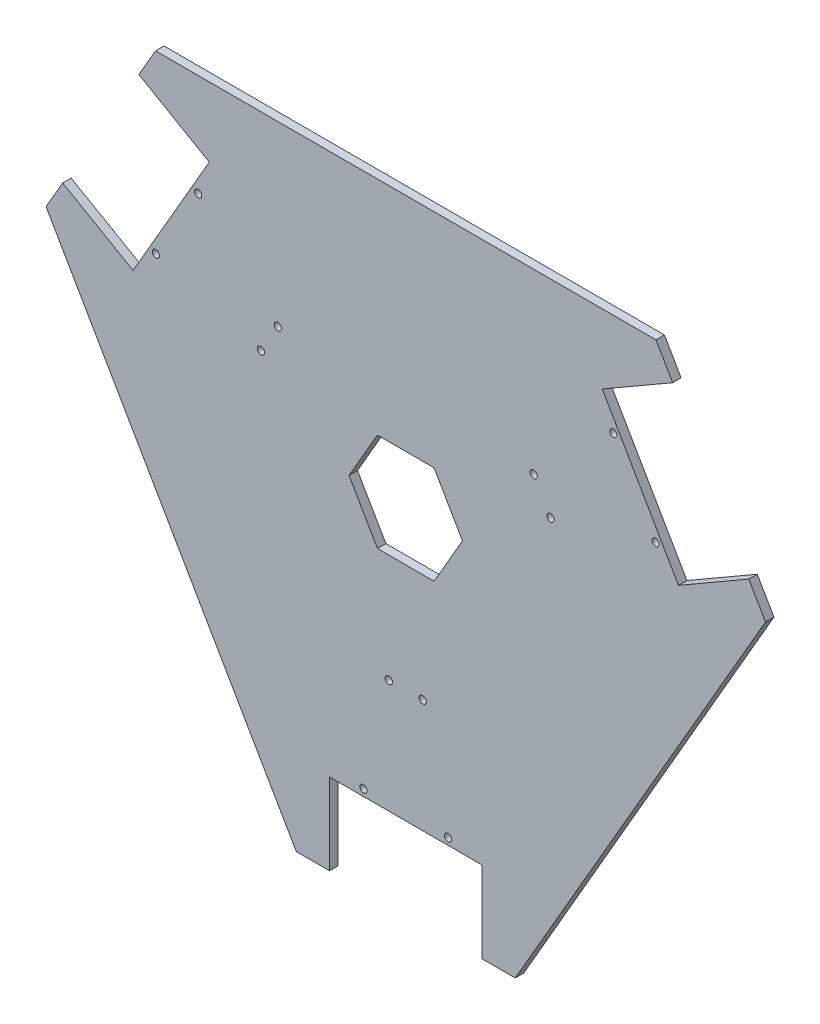
SolidWorks part; units mm, degrees
material "5052-O"
ref_plane "前基準面" through (0, 0, 0) normal (0, 0, 1) x (1, 0, 0)
ref_plane "上基準面" through (0, 0, 0) normal (0, 1, 0) x (1, 0, 0)
ref_plane "右基準面" through (0, 0, 0) normal (1, 0, 0) x (0, 0, -1)
ref_axis "基準軸1" through (0, 0, -0.25) along (0, 0, 1)
sketch "草圖1" plane through (0, 0, 0) normal (0, 0, 1) x (1, 0, 0)
  line L7 (0, -320) -> (277.1281, 160)
  line L8 (277.1281, 160) -> (-277.1281, 160)
  line L9 (-277.1281, 160) -> (0, -320)
  circle A1 centre (0, 0) radius 160 construction
  dimension "D1" = 320
extrude "填料-伸長1" add sketch "草圖1" along normal blind 5
sketch "草圖6" plane through (0, 0, 5) normal (0, 0, 1) x (1, 0, 0)
  line L0 (-64.6632, -208) -> (-45, -208)
  line L1 (-277.1281, 160) -> (0, -320) construction
  line L2 (-45, -208) -> (-45, -160)
  line L3 (-45, -160) -> (45, -160)
  line L4 (45, -160) -> (45, -208)
  line L5 (45, -208) -> (64.6632, -208)
  line L6 (0, -320) -> (277.1281, 160) construction
  line L7 (64.6632, -208) -> (0, -320)
  line L8 (0, -320) -> (-64.6632, -208)
  dimension "D1" = 90
  dimension "D2" = 160
  dimension "D3" = 48
extrude "除料-伸長1" cut sketch "草圖6" against normal through all
hole_wizard "M5x0.8 螺紋孔1" positions "草圖4" profile "草圖5" tap size "M5x0.8" standard "Ansi Metric" end condition through all
sketch "草圖4" plane through (0, 0, 5) normal (0, 0, 1) x (1, 0, 0)
  line L0 (0, -160) -> (0, -156) construction
  line L4 (-25, -156) -> (25, -156) construction
  line L5 (45, -160) -> (-45, -160) construction
  point P10 (-25, -156)
  point P11 (25, -156)
  dimension "D1" = 4
  dimension "D2" = 50
sketch "草圖5" plane through (25, -156, 5) normal (1, 0, 0) x (0, -1, 0)
  line L0 (0, 0) -> (0, 5)
  line L1 (0, 5) -> (2.1, 5)
  line L2 (2.1, 5) -> (2.1, 0)
  line L5 (2.1, 0) -> (0, 0)
  line L11 (0, -6.35) -> (0, 107.95) construction
  dimension "貫穿螺孔鑽直徑" = 4.2
  dimension "貫穿螺孔鑽深度" = 5
hole_wizard "M4 餘隙孔1" positions "草圖9" profile "草圖10" hole size "M4" standard "Ansi Metric" end condition through all
sketch "草圖9" plane through (0, 0, 5) normal (0, 0, 1) x (1, 0, 0)
  line L0 (-25, -156) -> (25, -156) construction
  line L3 (0, -156) -> (0, -93) construction
  line L6 (-10, -93) -> (10, -93) construction
  point P14 (-10, -93)
  point P15 (10, -93)
  dimension "D1" = 20
  dimension "D2" = 63
sketch "草圖10" plane through (10, -93, 5) normal (1, 0, 0) x (0, -1, 0)
  line L0 (0, 0) -> (0, 5)
  line L1 (0, 5) -> (2.15, 5)
  line L2 (2.15, 5) -> (2.15, 0)
  line L5 (2.15, 0) -> (0, 0)
  line L11 (0, -6.35) -> (0, 107.95) construction
  dimension "貫穿孔直徑" = 4.3
  dimension "貫穿孔深度" = 5
pattern_circular "環狀複製排列1" count 3 over 360 about axis through (0, 0, -0.25) along (0, 0, 1) of "M5x0.8 螺紋孔1", "除料-伸長1", "M4 餘隙孔1"
sketch "草圖11" plane through (0, 0, 5) normal (0, 0, 1) x (1, 0, 0)
  line L7 (33.4863, 0) -> (16.7432, 29)
  line L8 (16.7432, 29) -> (-16.7432, 29)
  line L9 (-16.7432, 29) -> (-33.4863, 0)
  line L10 (-33.4863, 0) -> (-16.7432, -29)
  line L11 (-16.7432, -29) -> (16.7432, -29)
  line L12 (16.7432, -29) -> (33.4863, 0)
  circle A1 centre (0, 0) radius 29 construction
  dimension "D1" = 58
extrude "除料-伸長2" cut sketch "草圖11" against normal through all
